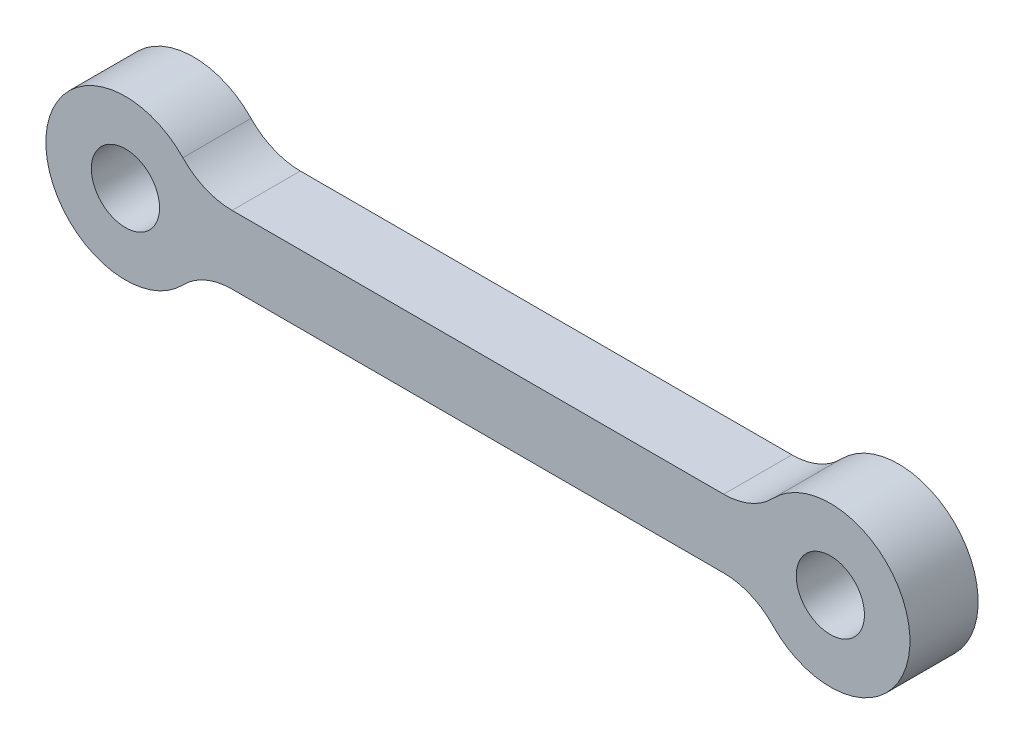
SolidWorks part; units mm, degrees
material "PET"
ref_plane "Front Plane" through (0, 0, 0) normal (0, 0, 1) x (1, 0, 0)
ref_plane "Top Plane" through (0, 0, 0) normal (0, 1, 0) x (1, 0, 0)
ref_plane "Right Plane" through (0, 0, 0) normal (1, 0, 0) x (0, 0, -1)
sketch "Sketch1" plane through (0, 0, 0) normal (0, 0, 1) x (1, 0, 0)
  line L0 (0, 0) -> (31, 0) construction
  line L1 (0, 3.5) -> (31, 3.5) construction
  line L2 (0, -3.5) -> (31, -3.5) construction
  line L3 (15.5, 0) -> (15.5, -3.5) construction
  line L5 (3.1623, 1.5) -> (27.8377, 1.5)
  line L6 (3.1623, 1.5) -> (3.1623, -1.5) construction
  line L7 (3.1623, -1.5) -> (27.8377, -1.5)
  line L8 (27.8377, 1.5) -> (27.8377, -1.5) construction
  line L9 (3.1623, 1.5) -> (27.8377, -1.5) construction
  line L10 (3.1623, -1.5) -> (27.8377, 1.5) construction
  arc A0 (0, 3.5) -> (0, -3.5) centre (0, 0) ccw construction
  arc A1 (31, -3.5) -> (31, 3.5) centre (31, 0) ccw construction
  circle A2 centre (0, 0) radius 1.5
  circle A3 centre (0, 0) radius 3.5
  circle A4 centre (31, 0) radius 1.5
  circle A5 centre (31, 0) radius 3.5
  point P3 (15.5, 0)
  point P20 (15.5, 1.5)
  dimension "D3" = 3
  dimension "D1" = 31
  dimension "D2" = 7
extrude "Boss-Extrude1" add sketch "Sketch1" along normal blind 3 contours A3 A2 | A5 L5 A3 L7 | A5 A4 region at (15.5, 0, 0) region at (3.3179, 0.747, 0) region at (31.747, 3.3179, 0)
fillet "Fillet1" radius 3 4 edges at (27.8377, -1.5, 1.5) (3.1623, -1.5, 1.5) (27.8377, 1.5, 1.5) (3.1623, 1.5, 1.5)
ref_axis "Axis1" through (0, 0, 18.1845) along (0, 0, -1)
